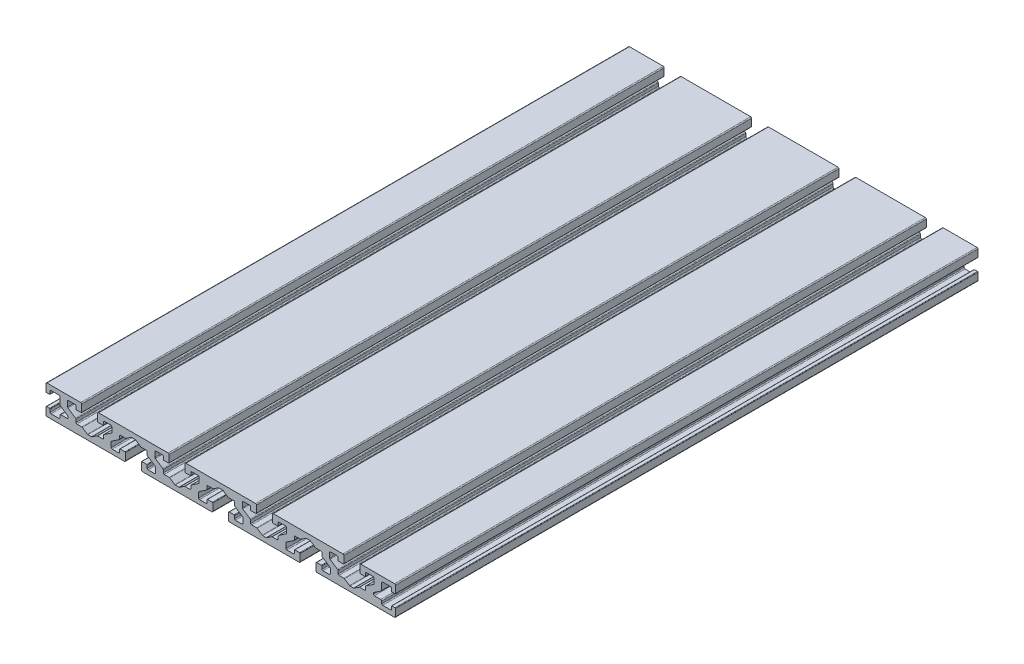
SolidWorks part; units mm, degrees
material "6063-T5"
ref_plane "Front Plane" through (0, 0, 0) normal (0, 0, 1) x (1, 0, 0)
ref_plane "Top Plane" through (0, 0, 0) normal (0, 1, 0) x (1, 0, 0)
ref_plane "Right Plane" through (0, 0, 0) normal (1, 0, 0) x (0, 0, -1)
sketch "Sketch1" plane through (0, 0, 0) normal (0, 0, 1) x (1, 0, 0)
  line L0 (0.5, 0) -> (40.4, 0)
  line L1 (180, 0.5) -> (180, 4.15)
  line L2 (179.5, 15) -> (162.1, 15)
  line L3 (0, 14.5) -> (0, 10.85)
  line L4 (179.75, 4.4) -> (178.15, 4.4)
  line L5 (0.25, 4.4) -> (1.85, 4.4)
  line L6 (179.75, 10.6) -> (178.15, 10.6)
  line L7 (0.25, 10.6) -> (1.85, 10.6)
  line L8 (0, 4.15) -> (0, 0.5)
  line L9 (180, 10.85) -> (180, 14.5)
  line L10 (71.6, 14.5) -> (71.6, 10.85)
  line L11 (18.4, 14.5) -> (18.4, 10.85)
  line L12 (26.6, 14.5) -> (26.6, 10.85)
  line L13 (17.9, 15) -> (0.5, 15)
  line L14 (63.4, 14.5) -> (63.4, 10.85)
  line L15 (116.6, 14.5) -> (116.6, 10.85)
  line L16 (108.4, 14.5) -> (108.4, 10.85)
  line L17 (161.6, 14.5) -> (161.6, 10.85)
  line L18 (153.4, 14.5) -> (153.4, 10.85)
  line L19 (62.9, 15) -> (27.1, 15)
  line L20 (107.9, 15) -> (72.1, 15)
  line L21 (152.9, 15) -> (117.1, 15)
  line L22 (85.9, 0.5) -> (85.9, 4.15)
  line L23 (40.9, 0.5) -> (40.9, 4.15)
  line L24 (49.1, 0.5) -> (49.1, 4.15)
  line L25 (49.6, 0) -> (85.4, 0)
  line L26 (94.1, 0.5) -> (94.1, 4.15)
  line L27 (130.9, 0.5) -> (130.9, 4.15)
  line L28 (139.1, 0.5) -> (139.1, 4.15)
  line L29 (94.6, 0) -> (130.4, 0)
  line L30 (139.6, 0) -> (179.5, 0)
  line L31 (63.15, 10.6) -> (60.65, 10.6)
  line L32 (26.85, 10.6) -> (29.35, 10.6)
  line L33 (18.15, 10.6) -> (15.65, 10.6)
  line L34 (71.85, 10.6) -> (74.35, 10.6)
  line L35 (108.15, 10.6) -> (105.65, 10.6)
  line L36 (116.85, 10.6) -> (119.35, 10.6)
  line L37 (153.15, 10.6) -> (150.65, 10.6)
  line L38 (161.85, 10.6) -> (164.35, 10.6)
  line L39 (40.65, 4.4) -> (38.15, 4.4)
  line L40 (49.35, 4.4) -> (51.85, 4.4)
  line L41 (85.65, 4.4) -> (83.15, 4.4)
  line L42 (94.35, 4.4) -> (96.85, 4.4)
  line L43 (130.65, 4.4) -> (128.15, 4.4)
  line L44 (139.35, 4.4) -> (141.85, 4.4)
  line L45 (52.6, 2.3) -> (55.9, 2.3)
  line L46 (2.6, 2.3) -> (6.6, 2.3)
  line L47 (7.1, 12.2) -> (7.1, 8.7315)
  line L48 (172.9, 12.2) -> (172.9, 8.7315)
  line L49 (6.6, 12.7) -> (2.6, 12.7)
  line L50 (15.4, 10.85) -> (15.4, 12.2)
  line L51 (29.6, 10.85) -> (29.6, 12.2)
  line L52 (74.6, 10.85) -> (74.6, 12.2)
  line L53 (60.4, 10.85) -> (60.4, 12.2)
  line L54 (119.6, 10.85) -> (119.6, 12.2)
  line L55 (105.4, 10.85) -> (105.4, 12.2)
  line L56 (164.6, 10.85) -> (164.6, 12.2)
  line L57 (150.4, 10.85) -> (150.4, 12.2)
  line L58 (37.9, 4.15) -> (37.9, 2.8)
  line L59 (52.1, 4.15) -> (52.1, 2.8)
  line L60 (97.1, 4.15) -> (97.1, 2.8)
  line L61 (82.9, 4.15) -> (82.9, 2.8)
  line L62 (142.1, 4.15) -> (142.1, 2.8)
  line L63 (127.9, 4.15) -> (127.9, 2.8)
  line L64 (56.1, 12.2) -> (56.1, 9.6704)
  line L65 (78.9, 12.2) -> (78.9, 9.6704)
  line L66 (33.9, 12.2) -> (33.9, 9.6704)
  line L67 (30.1, 12.7) -> (33.4, 12.7)
  line L68 (123.6774, 9.2543) -> (119.8226, 6.6845)
  line L69 (21.6056, 2.5) -> (23.3944, 2.5)
  line L70 (11.6, 12.7) -> (14.9, 12.7)
  line L71 (75.1, 12.7) -> (78.4, 12.7)
  line L72 (56.6, 12.7) -> (59.9, 12.7)
  line L73 (120.1, 12.7) -> (123.4, 12.7)
  line L74 (101.6, 12.7) -> (104.9, 12.7)
  line L75 (165.1, 12.7) -> (168.4, 12.7)
  line L76 (146.6, 12.7) -> (149.9, 12.7)
  line L77 (66.6056, 2.5) -> (68.3944, 2.5)
  line L78 (56.3226, 9.2543) -> (60.1774, 6.6845)
  line L79 (101.1, 12.2) -> (101.1, 9.6704)
  line L80 (37.4, 2.3) -> (34.1, 2.3)
  line L81 (97.6, 2.3) -> (100.9, 2.3)
  line L82 (82.4, 2.3) -> (79.1, 2.3)
  line L83 (142.6, 2.3) -> (145.9, 2.3)
  line L84 (127.4, 2.3) -> (124.1, 2.3)
  line L85 (33.6, 2.8) -> (33.6, 5.3296)
  line L86 (56.4, 2.8) -> (56.4, 5.3296)
  line L87 (101.4, 2.8) -> (101.4, 5.3296)
  line L88 (91.1718, 12.416) -> (93.7699, 10.684)
  line L89 (89.1056, 12.5) -> (90.8944, 12.5)
  line L90 (78.8226, 5.7457) -> (82.6774, 8.3155)
  line L91 (168.6774, 9.2543) -> (164.8226, 6.6845)
  line L92 (29.6, 4.9) -> (29.6, 6.2685)
  line L93 (18.4528, 4.4) -> (15.9, 4.4)
  line L94 (26.5472, 4.4) -> (29.1, 4.4)
  line L95 (123.9, 12.2) -> (123.9, 9.6704)
  line L96 (7.3226, 8.3155) -> (11.1774, 5.7457)
  line L97 (15.4, 4.9) -> (15.4, 6.2685)
  line L98 (18.7301, 4.316) -> (21.3282, 2.584)
  line L99 (2.1, 4.15) -> (2.1, 2.8)
  line L100 (2.1, 12.2) -> (2.1, 10.85)
  line L101 (173.4, 12.7) -> (177.4, 12.7)
  line L102 (177.9, 12.2) -> (177.9, 10.85)
  line L103 (173.4, 2.3) -> (177.4, 2.3)
  line L104 (177.9, 2.8) -> (177.9, 4.15)
  line L105 (26.2699, 4.316) -> (23.6718, 2.584)
  line L106 (44.1056, 12.5) -> (45.8944, 12.5)
  line L107 (33.6774, 9.2543) -> (29.8226, 6.6845)
  line L108 (111.6056, 2.5) -> (113.3944, 2.5)
  line L109 (101.3226, 9.2543) -> (105.1774, 6.6845)
  line L110 (146.1, 12.2) -> (146.1, 9.6704)
  line L111 (168.9, 12.2) -> (168.9, 9.6704)
  line L112 (74.6, 4.9) -> (74.6, 6.2685)
  line L113 (156.6056, 2.5) -> (158.3944, 2.5)
  line L114 (97.1, 10.1) -> (97.1, 8.7315)
  line L115 (11.1, 12.2) -> (11.1, 9.6704)
  line L116 (11.3226, 9.2543) -> (15.1774, 6.6845)
  line L117 (146.3226, 9.2543) -> (150.1774, 6.6845)
  line L118 (78.6, 2.8) -> (78.6, 5.3296)
  line L119 (146.4, 2.8) -> (146.4, 5.3296)
  line L120 (33.8226, 5.7457) -> (37.6774, 8.3155)
  line L121 (136.1718, 12.416) -> (138.7699, 10.684)
  line L122 (134.1056, 12.5) -> (135.8944, 12.5)
  line L123 (46.1718, 12.416) -> (48.7699, 10.684)
  line L124 (123.8226, 5.7457) -> (127.6774, 8.3155)
  line L125 (123.6, 2.8) -> (123.6, 5.3296)
  line L126 (78.6774, 9.2543) -> (74.8226, 6.6845)
  line L127 (71.5472, 4.4) -> (74.1, 4.4)
  line L128 (63.4528, 4.4) -> (60.9, 4.4)
  line L129 (60.4, 4.9) -> (60.4, 6.2685)
  line L130 (119.6, 4.9) -> (119.6, 6.2685)
  line L131 (116.5472, 4.4) -> (119.1, 4.4)
  line L132 (108.4528, 4.4) -> (105.9, 4.4)
  line L133 (105.4, 4.9) -> (105.4, 6.2685)
  line L134 (164.6, 4.9) -> (164.6, 6.2685)
  line L135 (161.5472, 4.4) -> (164.1, 4.4)
  line L136 (153.4528, 4.4) -> (150.9, 4.4)
  line L137 (150.4, 4.9) -> (150.4, 6.2685)
  line L138 (63.7301, 4.316) -> (66.3282, 2.584)
  line L139 (71.2699, 4.316) -> (68.6718, 2.584)
  line L140 (108.7301, 4.316) -> (111.3282, 2.584)
  line L141 (116.2699, 4.316) -> (113.6718, 2.584)
  line L142 (153.7301, 4.316) -> (156.3282, 2.584)
  line L143 (161.2699, 4.316) -> (158.6718, 2.584)
  line L144 (11.4, 4.9) -> (11.4, 5.3296)
  line L145 (49.0472, 10.6) -> (51.6, 10.6)
  line L146 (40.9528, 10.6) -> (38.4, 10.6)
  line L147 (37.9, 10.1) -> (37.9, 8.7315)
  line L148 (52.1, 10.1) -> (52.1, 8.7315)
  line L149 (41.2301, 10.684) -> (43.8282, 12.416)
  line L150 (52.3226, 8.3155) -> (56.1774, 5.7457)
  line L151 (94.0472, 10.6) -> (96.6, 10.6)
  line L152 (85.9528, 10.6) -> (83.4, 10.6)
  line L153 (82.9, 10.1) -> (82.9, 8.7315)
  line L154 (142.1, 10.1) -> (142.1, 8.7315)
  line L155 (139.0472, 10.6) -> (141.6, 10.6)
  line L156 (130.9528, 10.6) -> (128.4, 10.6)
  line L157 (127.9, 10.1) -> (127.9, 8.7315)
  line L158 (86.2301, 10.684) -> (88.8282, 12.416)
  line L159 (97.3226, 8.3155) -> (101.1774, 5.7457)
  line L160 (131.2301, 10.684) -> (133.8282, 12.416)
  line L161 (142.3226, 8.3155) -> (146.1774, 5.7457)
  line L162 (7.6, 4.4) -> (10.9, 4.4)
  line L163 (7.1, 3.9) -> (7.1, 2.8)
  line L164 (7.1, 2.3) -> (11.4, 2.3) [skipped]
  line L166 (168.8226, 5.7457) -> (172.6774, 8.3155)
  line L167 (168.6, 4.9) -> (168.6, 5.3296)
  line L170 (172.4, 4.4) -> (169.1, 4.4)
  line L171 (172.9, 3.9) -> (172.9, 2.8)
  line L172 (172.9, 2.3) -> (168.6, 2.3) [skipped]
  line L173 (7.1, 3.9) -> (7.1, 2.3) [skipped]
  line L174 (172.9, 3.9) -> (172.9, 2.3) [skipped]
  arc A0 (0.5, 0) -> (0, 0.5) centre (0.5, 0.5) cw
  arc A1 (0.5, 15) -> (0, 14.5) centre (0.5, 14.5) ccw
  arc A2 (179.5, 0) -> (180, 0.5) centre (179.5, 0.5) ccw
  arc A3 (180, 14.5) -> (179.5, 15) centre (179.5, 14.5) ccw
  arc A4 (161.6, 14.5) -> (162.1, 15) centre (162.1, 14.5) cw
  arc A5 (153.4, 14.5) -> (152.9, 15) centre (152.9, 14.5) ccw
  arc A6 (139.1, 0.5) -> (139.6, 0) centre (139.6, 0.5) ccw
  arc A7 (130.9, 0.5) -> (130.4, 0) centre (130.4, 0.5) cw
  arc A8 (108.4, 14.5) -> (107.9, 15) centre (107.9, 14.5) ccw
  arc A9 (116.6, 14.5) -> (117.1, 15) centre (117.1, 14.5) cw
  arc A10 (85.9, 0.5) -> (85.4, 0) centre (85.4, 0.5) cw
  arc A11 (94.1, 0.5) -> (94.6, 0) centre (94.6, 0.5) ccw
  arc A12 (71.6, 14.5) -> (72.1, 15) centre (72.1, 14.5) cw
  arc A13 (63.4, 14.5) -> (62.9, 15) centre (62.9, 14.5) ccw
  arc A14 (49.6, 0) -> (49.1, 0.5) centre (49.6, 0.5) cw
  arc A15 (40.4, 0) -> (40.9, 0.5) centre (40.4, 0.5) ccw
  arc A16 (17.9, 15) -> (18.4, 14.5) centre (17.9, 14.5) cw
  arc A17 (27.1, 15) -> (26.6, 14.5) centre (27.1, 14.5) ccw
  arc A18 (7.1, 3.9) -> (7.6, 4.4) centre (7.6, 3.9) cw
  arc A19 (10.9, 4.4) -> (11.4, 4.9) centre (10.9, 4.9) ccw
  arc A20 (11.1774, 5.7457) -> (11.4, 5.3296) centre (10.9, 5.3296) cw
  arc A21 (7.3226, 8.3155) -> (7.1, 8.7315) centre (7.6, 8.7315) cw
  arc A22 (2.1, 2.8) -> (2.6, 2.3) centre (2.6, 2.8) ccw
  arc A23 (7.1, 2.8) -> (6.6, 2.3) centre (6.6, 2.8) cw
  arc A24 (7.1, 12.2) -> (6.6, 12.7) centre (6.6, 12.2) ccw
  arc A25 (2.6, 12.7) -> (2.1, 12.2) centre (2.6, 12.2) ccw
  arc A26 (29.6, 12.2) -> (30.1, 12.7) centre (30.1, 12.2) cw
  arc A27 (33.4, 12.7) -> (33.9, 12.2) centre (33.4, 12.2) cw
  arc A28 (33.9, 9.6704) -> (33.6774, 9.2543) centre (33.4, 9.6704) cw
  arc A29 (29.6, 6.2685) -> (29.8226, 6.6845) centre (30.1, 6.2685) cw
  arc A30 (29.1, 4.4) -> (29.6, 4.9) centre (29.1, 4.9) ccw
  arc A31 (26.5472, 4.4) -> (26.2699, 4.316) centre (26.5472, 3.9) ccw
  arc A32 (23.3944, 2.5) -> (23.6718, 2.584) centre (23.3944, 3) ccw
  arc A33 (21.6056, 2.5) -> (21.3282, 2.584) centre (21.6056, 3) cw
  arc A34 (18.4528, 4.4) -> (18.7301, 4.316) centre (18.4528, 3.9) cw
  arc A35 (15.9, 4.4) -> (15.4, 4.9) centre (15.9, 4.9) cw
  arc A36 (15.4, 6.2685) -> (15.1774, 6.6845) centre (14.9, 6.2685) ccw
  arc A37 (11.1, 9.6704) -> (11.3226, 9.2543) centre (11.6, 9.6704) ccw
  arc A38 (11.6, 12.7) -> (11.1, 12.2) centre (11.6, 12.2) ccw
  arc A39 (14.9, 12.7) -> (15.4, 12.2) centre (14.9, 12.2) cw
  arc A40 (52.1, 2.8) -> (52.6, 2.3) centre (52.6, 2.8) ccw
  arc A41 (55.9, 2.3) -> (56.4, 2.8) centre (55.9, 2.8) ccw
  arc A42 (56.4, 5.3296) -> (56.1774, 5.7457) centre (55.9, 5.3296) ccw
  arc A43 (52.1, 8.7315) -> (52.3226, 8.3155) centre (52.6, 8.7315) ccw
  arc A44 (51.6, 10.6) -> (52.1, 10.1) centre (51.6, 10.1) cw
  arc A45 (48.7699, 10.684) -> (49.0472, 10.6) centre (49.0472, 11.1) ccw
  arc A46 (45.8944, 12.5) -> (46.1718, 12.416) centre (45.8944, 12) cw
  arc A47 (44.1056, 12.5) -> (43.8282, 12.416) centre (44.1056, 12) ccw
  arc A48 (41.2301, 10.684) -> (40.9528, 10.6) centre (40.9528, 11.1) cw
  arc A49 (38.4, 10.6) -> (37.9, 10.1) centre (38.4, 10.1) ccw
  arc A50 (37.9, 8.7315) -> (37.6774, 8.3155) centre (37.4, 8.7315) cw
  arc A51 (33.6, 5.3296) -> (33.8226, 5.7457) centre (34.1, 5.3296) cw
  arc A52 (34.1, 2.3) -> (33.6, 2.8) centre (34.1, 2.8) cw
  arc A53 (37.9, 2.8) -> (37.4, 2.3) centre (37.4, 2.8) cw
  arc A54 (60.4, 6.2685) -> (60.1774, 6.6845) centre (59.9, 6.2685) ccw
  arc A55 (60.9, 4.4) -> (60.4, 4.9) centre (60.9, 4.9) cw
  arc A56 (63.4528, 4.4) -> (63.7301, 4.316) centre (63.4528, 3.9) cw
  arc A57 (66.6056, 2.5) -> (66.3282, 2.584) centre (66.6056, 3) cw
  arc A58 (68.6718, 2.584) -> (68.3944, 2.5) centre (68.3944, 3) cw
  arc A59 (71.5472, 4.4) -> (71.2699, 4.316) centre (71.5472, 3.9) ccw
  arc A60 (74.6, 4.9) -> (74.1, 4.4) centre (74.1, 4.9) cw
  arc A61 (74.6, 6.2685) -> (74.8226, 6.6845) centre (75.1, 6.2685) cw
  arc A62 (78.9, 9.6704) -> (78.6774, 9.2543) centre (78.4, 9.6704) cw
  arc A63 (78.9, 12.2) -> (78.4, 12.7) centre (78.4, 12.2) ccw
  arc A64 (74.6, 12.2) -> (75.1, 12.7) centre (75.1, 12.2) cw
  arc A65 (56.1, 9.6704) -> (56.3226, 9.2543) centre (56.6, 9.6704) ccw
  arc A66 (56.1, 12.2) -> (56.6, 12.7) centre (56.6, 12.2) cw
  arc A67 (60.4, 12.2) -> (59.9, 12.7) centre (59.9, 12.2) ccw
  arc A68 (119.6, 12.2) -> (120.1, 12.7) centre (120.1, 12.2) cw
  arc A69 (123.4, 12.7) -> (123.9, 12.2) centre (123.4, 12.2) cw
  arc A70 (123.9, 9.6704) -> (123.6774, 9.2543) centre (123.4, 9.6704) cw
  arc A71 (119.6, 6.2685) -> (119.8226, 6.6845) centre (120.1, 6.2685) cw
  arc A72 (119.6, 4.9) -> (119.1, 4.4) centre (119.1, 4.9) cw
  arc A73 (116.5472, 4.4) -> (116.2699, 4.316) centre (116.5472, 3.9) ccw
  arc A74 (113.6718, 2.584) -> (113.3944, 2.5) centre (113.3944, 3) cw
  arc A75 (111.6056, 2.5) -> (111.3282, 2.584) centre (111.6056, 3) cw
  arc A76 (108.4528, 4.4) -> (108.7301, 4.316) centre (108.4528, 3.9) cw
  arc A77 (105.9, 4.4) -> (105.4, 4.9) centre (105.9, 4.9) cw
  arc A78 (105.4, 6.2685) -> (105.1774, 6.6845) centre (104.9, 6.2685) ccw
  arc A79 (101.1, 9.6704) -> (101.3226, 9.2543) centre (101.6, 9.6704) ccw
  arc A80 (101.6, 12.7) -> (101.1, 12.2) centre (101.6, 12.2) ccw
  arc A81 (105.4, 12.2) -> (104.9, 12.7) centre (104.9, 12.2) ccw
  arc A82 (82.9, 8.7315) -> (82.6774, 8.3155) centre (82.4, 8.7315) cw
  arc A83 (78.8226, 5.7457) -> (78.6, 5.3296) centre (79.1, 5.3296) ccw
  arc A84 (78.6, 2.8) -> (79.1, 2.3) centre (79.1, 2.8) ccw
  arc A85 (82.9, 2.8) -> (82.4, 2.3) centre (82.4, 2.8) cw
  arc A86 (97.1, 2.8) -> (97.6, 2.3) centre (97.6, 2.8) ccw
  arc A87 (101.4, 2.8) -> (100.9, 2.3) centre (100.9, 2.8) cw
  arc A88 (101.4, 5.3296) -> (101.1774, 5.7457) centre (100.9, 5.3296) ccw
  arc A89 (97.1, 8.7315) -> (97.3226, 8.3155) centre (97.6, 8.7315) ccw
  arc A90 (97.1, 10.1) -> (96.6, 10.6) centre (96.6, 10.1) ccw
  arc A91 (94.0472, 10.6) -> (93.7699, 10.684) centre (94.0472, 11.1) cw
  arc A92 (91.1718, 12.416) -> (90.8944, 12.5) centre (90.8944, 12) ccw
  arc A93 (89.1056, 12.5) -> (88.8282, 12.416) centre (89.1056, 12) ccw
  arc A94 (85.9528, 10.6) -> (86.2301, 10.684) centre (85.9528, 11.1) ccw
  arc A95 (83.4, 10.6) -> (82.9, 10.1) centre (83.4, 10.1) ccw
  arc A96 (164.6, 12.2) -> (165.1, 12.7) centre (165.1, 12.2) cw
  arc A97 (168.4, 12.7) -> (168.9, 12.2) centre (168.4, 12.2) cw
  arc A98 (168.9, 9.6704) -> (168.6774, 9.2543) centre (168.4, 9.6704) cw
  arc A99 (164.6, 6.2685) -> (164.8226, 6.6845) centre (165.1, 6.2685) cw
  arc A100 (164.6, 4.9) -> (164.1, 4.4) centre (164.1, 4.9) cw
  arc A101 (161.5472, 4.4) -> (161.2699, 4.316) centre (161.5472, 3.9) ccw
  arc A102 (158.6718, 2.584) -> (158.3944, 2.5) centre (158.3944, 3) cw
  arc A103 (156.6056, 2.5) -> (156.3282, 2.584) centre (156.6056, 3) cw
  arc A104 (153.4528, 4.4) -> (153.7301, 4.316) centre (153.4528, 3.9) cw
  arc A105 (150.9, 4.4) -> (150.4, 4.9) centre (150.9, 4.9) cw
  arc A106 (150.4, 6.2685) -> (150.1774, 6.6845) centre (149.9, 6.2685) ccw
  arc A107 (146.1, 9.6704) -> (146.3226, 9.2543) centre (146.6, 9.6704) ccw
  arc A108 (146.6, 12.7) -> (146.1, 12.2) centre (146.6, 12.2) ccw
  arc A109 (150.4, 12.2) -> (149.9, 12.7) centre (149.9, 12.2) ccw
  arc A110 (142.1, 2.8) -> (142.6, 2.3) centre (142.6, 2.8) ccw
  arc A111 (145.9, 2.3) -> (146.4, 2.8) centre (145.9, 2.8) ccw
  arc A112 (146.4, 5.3296) -> (146.1774, 5.7457) centre (145.9, 5.3296) ccw
  arc A113 (142.1, 8.7315) -> (142.3226, 8.3155) centre (142.6, 8.7315) ccw
  arc A114 (142.1, 10.1) -> (141.6, 10.6) centre (141.6, 10.1) ccw
  arc A115 (139.0472, 10.6) -> (138.7699, 10.684) centre (139.0472, 11.1) cw
  arc A116 (136.1718, 12.416) -> (135.8944, 12.5) centre (135.8944, 12) ccw
  arc A117 (134.1056, 12.5) -> (133.8282, 12.416) centre (134.1056, 12) ccw
  arc A118 (130.9528, 10.6) -> (131.2301, 10.684) centre (130.9528, 11.1) ccw
  arc A119 (128.4, 10.6) -> (127.9, 10.1) centre (128.4, 10.1) ccw
  arc A120 (127.9, 8.7315) -> (127.6774, 8.3155) centre (127.4, 8.7315) cw
  arc A121 (123.8226, 5.7457) -> (123.6, 5.3296) centre (124.1, 5.3296) ccw
  arc A122 (124.1, 2.3) -> (123.6, 2.8) centre (124.1, 2.8) cw
  arc A123 (127.9, 2.8) -> (127.4, 2.3) centre (127.4, 2.8) cw
  arc A124 (172.6774, 8.3155) -> (172.9, 8.7315) centre (172.4, 8.7315) ccw
  arc A125 (168.8226, 5.7457) -> (168.6, 5.3296) centre (169.1, 5.3296) ccw
  arc A126 (169.1, 4.4) -> (168.6, 4.9) centre (169.1, 4.9) cw
  arc A127 (172.9, 3.9) -> (172.4, 4.4) centre (172.4, 3.9) ccw
  arc A128 (172.9, 2.8) -> (173.4, 2.3) centre (173.4, 2.8) ccw
  arc A129 (177.4, 2.3) -> (177.9, 2.8) centre (177.4, 2.8) ccw
  arc A130 (172.9, 12.2) -> (173.4, 12.7) centre (173.4, 12.2) cw
  arc A131 (177.4, 12.7) -> (177.9, 12.2) centre (177.4, 12.2) cw
  arc A132 (119.35, 10.6) -> (119.6, 10.85) centre (119.35, 10.85) ccw
  arc A133 (116.6, 10.85) -> (116.85, 10.6) centre (116.85, 10.85) ccw
  arc A134 (108.4, 10.85) -> (108.15, 10.6) centre (108.15, 10.85) cw
  arc A135 (105.65, 10.6) -> (105.4, 10.85) centre (105.65, 10.85) cw
  arc A136 (96.85, 4.4) -> (97.1, 4.15) centre (96.85, 4.15) cw
  arc A137 (94.1, 4.15) -> (94.35, 4.4) centre (94.35, 4.15) cw
  arc A138 (85.65, 4.4) -> (85.9, 4.15) centre (85.65, 4.15) cw
  arc A139 (82.9, 4.15) -> (83.15, 4.4) centre (83.15, 4.15) cw
  arc A140 (74.35, 10.6) -> (74.6, 10.85) centre (74.35, 10.85) ccw
  arc A141 (71.6, 10.85) -> (71.85, 10.6) centre (71.85, 10.85) ccw
  arc A142 (63.4, 10.85) -> (63.15, 10.6) centre (63.15, 10.85) cw
  arc A143 (60.65, 10.6) -> (60.4, 10.85) centre (60.65, 10.85) cw
  arc A144 (51.85, 4.4) -> (52.1, 4.15) centre (51.85, 4.15) cw
  arc A145 (49.1, 4.15) -> (49.35, 4.4) centre (49.35, 4.15) cw
  arc A146 (40.9, 4.15) -> (40.65, 4.4) centre (40.65, 4.15) ccw
  arc A147 (38.15, 4.4) -> (37.9, 4.15) centre (38.15, 4.15) ccw
  arc A148 (29.35, 10.6) -> (29.6, 10.85) centre (29.35, 10.85) ccw
  arc A149 (26.6, 10.85) -> (26.85, 10.6) centre (26.85, 10.85) ccw
  arc A150 (18.4, 10.85) -> (18.15, 10.6) centre (18.15, 10.85) cw
  arc A151 (15.65, 10.6) -> (15.4, 10.85) centre (15.65, 10.85) cw
  arc A152 (0, 4.15) -> (0.25, 4.4) centre (0.25, 4.15) cw
  arc A153 (1.85, 4.4) -> (2.1, 4.15) centre (1.85, 4.15) cw
  arc A154 (1.85, 10.6) -> (2.1, 10.85) centre (1.85, 10.85) ccw
  arc A155 (0, 10.85) -> (0.25, 10.6) centre (0.25, 10.85) ccw
  arc A156 (178.15, 4.4) -> (177.9, 4.15) centre (178.15, 4.15) ccw
  arc A157 (179.75, 4.4) -> (180, 4.15) centre (179.75, 4.15) cw
  arc A158 (179.75, 10.6) -> (180, 10.85) centre (179.75, 10.85) ccw
  arc A159 (178.15, 10.6) -> (177.9, 10.85) centre (178.15, 10.85) cw
  arc A160 (164.35, 10.6) -> (164.6, 10.85) centre (164.35, 10.85) ccw
  arc A161 (161.6, 10.85) -> (161.85, 10.6) centre (161.85, 10.85) ccw
  arc A162 (153.4, 10.85) -> (153.15, 10.6) centre (153.15, 10.85) cw
  arc A163 (150.65, 10.6) -> (150.4, 10.85) centre (150.65, 10.85) cw
  arc A164 (141.85, 4.4) -> (142.1, 4.15) centre (141.85, 4.15) cw
  arc A165 (139.1, 4.15) -> (139.35, 4.4) centre (139.35, 4.15) cw
  arc A166 (130.9, 4.15) -> (130.65, 4.4) centre (130.65, 4.15) ccw
  arc A167 (128.15, 4.4) -> (127.9, 4.15) centre (128.15, 4.15) ccw
  point P228 (7.1, 2.3)
  dimension "D3" = 2
  dimension "D1" = 2
  dimension "D4" = 3
  dimension "D2" = 3
extrude "Boss-Extrude1" add sketch "Sketch1" along normal blind 300 contours L19 A17 L12 A149 L32 A148 L51 A26 L67 A27 L66 A28 L107 A29 L92 A30 L94 A31 L105 A32 L69 A33 L98 A34 L93 A35 L97 A36 L116 A37 L115 A38 L70 A39 L50 A151 L33 A150 L11 A16 L13 A1 L3 A155 L7 A154 L100 A25 L49 A24 L47 A21 L96 A20 L144 A19 L162 A18 L163 A23 L46 A22 L99 A153 L5 A152 L8 A0 L0 A15 L23 A146 L39 A147 L58 A53 L80 A52 L85 A51 L120 A50 L147 A49 L146 A48 L149 A47 L106 A46 L123 A45 L145 A44 L148 A43 L150 A42 L86 A41 L45 A40 L59 A144 L40 A145 L24 A14 L25 A10 L22 A138 L41 A139 L61 A85 L82 A84 L118 A83 L90 A82 L153 A95 L152 A94 L158 A93 L89 A92 L88 A91 L151 A90 L114 A89 L159 A88 L87 A87 L81 A86 L60 A136 L42 A137 L26 A11 L29 A7 L27 A166 L43 A167 L63 A123 L84 A122 L125 A121 L124 A120 L157 A119 L156 A118 L160 A117 L122 A116 L121 A115 L155 A114 L154 A113 L161 A112 L119 A111 L83 A110 L62 A164 L44 A165 L28 A6 L30 A2 L1 A157 L4 A156 L104 A129 L103 A128 L171 A127 L170 A126 L167 A125 L166 A124 L48 A130 L101 A131 L102 A159 L6 A158 L9 A3 L2 A4 L17 A161 L38 A160 L56 A96 L75 A97 L111 A98 L91 A99 L134 A100 L135 A101 L143 A102 L113 A103 L142 A104 L136 A105 L137 A106 L117 A107 L110 A108 L76 A109 L57 A163 L37 A162 L18 A5 L21 A9 L15 A133 L36 A132 L54 A68 L73 A69 L95 A70 L68 A71 L130 A72 L131 A73 L141 A74 L108 A75 L140 A76 L132 A77 L133 A78 L109 A79 L79 A80 L74 A81 L55 A135 L35 A134 L16 A8 L20 A12 L10 A141 L34 A140 L52 A64 L71 A63 L65 A62 L126 A61 L112 A60 L127 A59 L139 A58 L77 A57 L138 A56 L128 A55 L129 A54 L78 A65 L64 A66 L72 A67 L53 A143 L31 A142 L14 A13
sketch "Sketch2" plane through (0, 0, 300) normal (0, 0, 1) x (1, 0, 0)
  line L0 (45, -987.5) -> (45, 49012.5) construction
  line L1 (44.1056, 12.5) -> (45.8944, 12.5) construction
  line L2 (135, -987.5) -> (135, 49012.5) construction
  line L3 (134.1056, 12.5) -> (135.8944, 12.5) construction
  line L4 (90, -987.5) -> (90, 49012.5) construction
  line L5 (89.1056, 12.5) -> (90.8944, 12.5) construction
  point P5 (45, 12.5)
  point P10 (135, 12.5)
  point P15 (90, 12.5)
